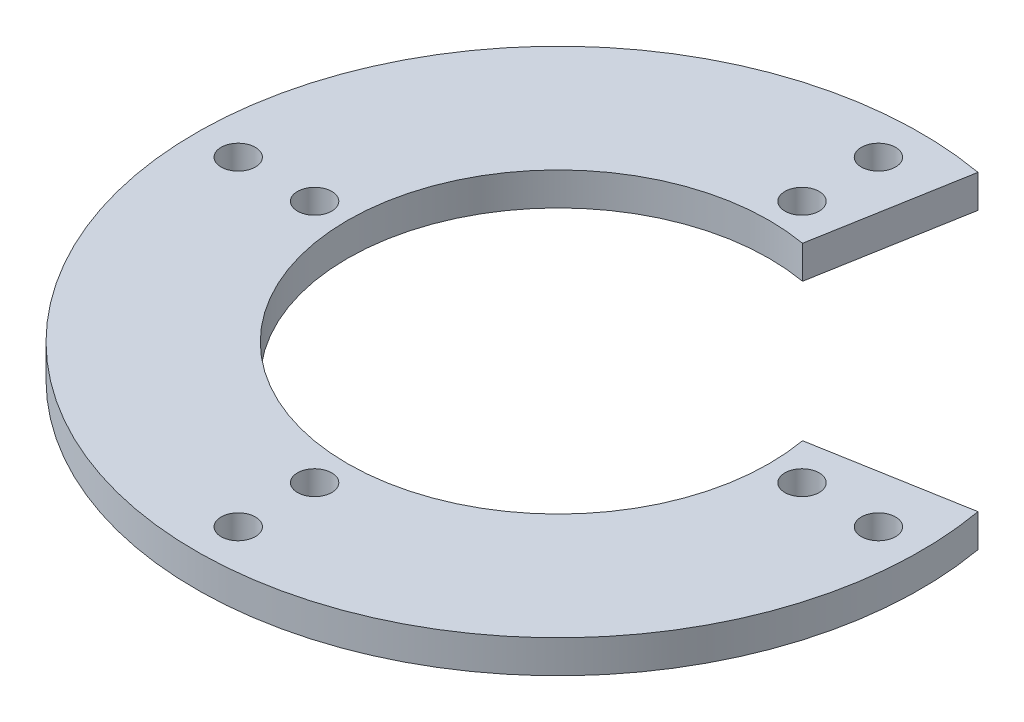
SolidWorks part; units mm, degrees
ref_plane "Front Plane" through (0, 0, 0) normal (0, 0, 1) x (1, 0, 0)
ref_plane "Top Plane" through (0, 0, 0) normal (0, 1, 0) x (1, 0, 0)
ref_plane "Right Plane" through (0, 0, 0) normal (1, 0, 0) x (0, 0, -1)
sketch "Sketch1" plane through (0, 0, 0) normal (0, 1, 0) x (1, 0, 0)
  line L0 (0, 18.5) -> (0, 0) construction
  line L1 (0, 0) -> (4.7753, 27.0822)
  line L2 (0, 0) -> (27.0822, 4.7753)
  line L3 (0, 0) -> (24.1467, 24.1467) construction
  line L4 (0, 0) -> (39.76, 0) construction
  circle A0 centre (0, 0) radius 18.5 construction
  circle A1 centre (0, 18.5) radius 1.3
  circle A2 centre (0, 0) radius 24.3 construction
  circle A3 centre (0, 24.3) radius 1.3
  circle A4 centre (0, 0) radius 27.5
  circle A5 centre (0, 0) radius 16
  circle A6 centre (18.5, 0) radius 1.3
  circle A7 centre (24.3, 0) radius 1.3
  circle A8 centre (0, -18.5) radius 1.3
  circle A9 centre (0, -24.3) radius 1.3
  circle A10 centre (-18.5, 0) radius 1.3
  circle A11 centre (-24.3, 0) radius 1.3
  point P28 (0, 0)
  dimension "D1" = 2.6
  dimension "D2" = 37
  dimension "D3" = 48.6
  dimension "D4" = 55
  dimension "D5" = 32
  dimension "D7" = 45
  dimension "D8" = 70
  dimension "D6" = 4
extrude "Boss-Extrude1" add sketch "Sketch1" along normal blind 2.5 contours A5 L1 A4 L2 A11 A10 A9 A8 A7 A6 A1 A3 region at (-12.8526, 0, 10.7846)
